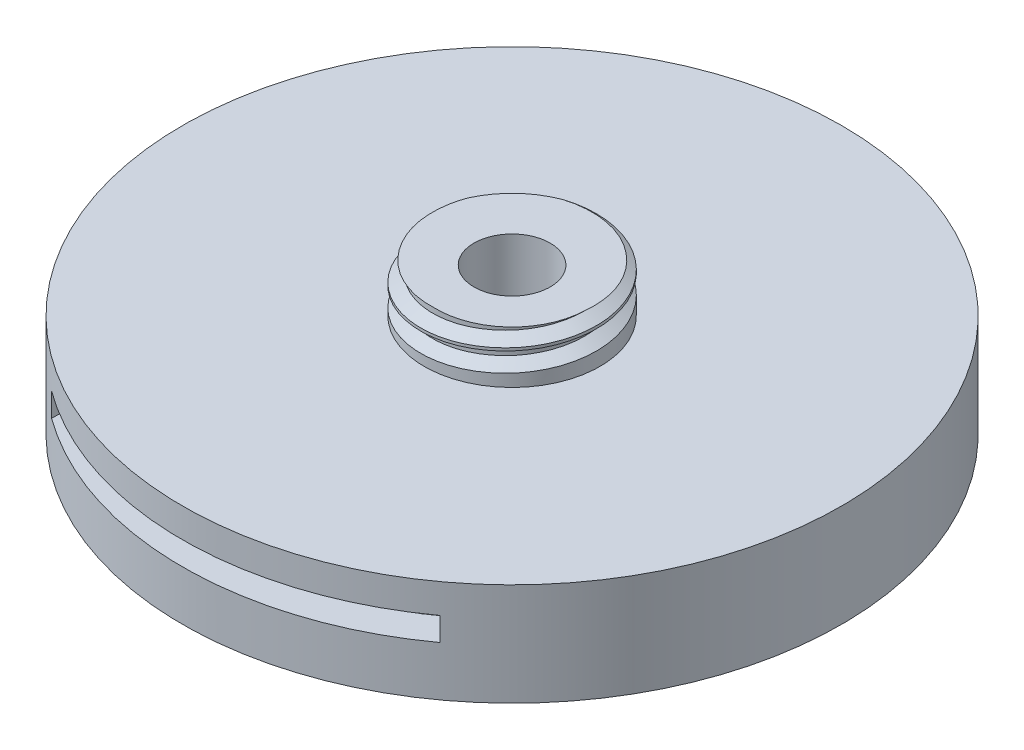
SolidWorks part; units mm, degrees
ref_plane "Ebene vorne" through (0, 0, 0) normal (0, 0, 1) x (1, 0, 0)
ref_plane "Ebene oben" through (0, 0, 0) normal (0, 1, 0) x (1, 0, 0)
ref_plane "Ebene rechts" through (0, 0, 0) normal (1, 0, 0) x (0, 0, -1)
sketch "Skizze1" plane through (0, 0, 0) normal (0, 1, 0) x (1, 0, 0)
  circle A0 centre (-18.0437, 0) radius 5
extrude "Zylinder" add sketch "Skizze1" along normal blind 2.2
ref_plane "Ebene auf Zylinder" through (0, 2.2, 0) normal (0, 1, 0) x (1, 0, 0)
sketch "Skizze4" plane through (0, 2.2, 0) normal (0, 1, 0) x (1, 0, 0)
  circle A0 centre (-18.0437, 0) radius 4.5
extrude "Schnitt-Linear austragen1" cut sketch "Skizze4" against normal blind 5 and the other way blind 10
ref_plane "Eben im Zylinder" through (0, 0.8, 0) normal (0, 1, 0) x (1, 0, 0)
sketch "Skizze5" plane through (0, 0.8, 0) normal (0, 1, 0) x (1, 0, 0)
  circle A0 centre (-18.0437, 0) radius 4.55
ref_plane "Ebene für Aufsatz" through (0, 0, 0) normal (0, -1, 0) x (-1, 0, 0)
sketch "Skizze6" plane through (0, 0, 0) normal (0, -1, 0) x (-1, 0, 0)
  circle A0 centre (18.0437, 0) radius 22.5
extrude "Fassung Objektträgergewinde" add sketch "Skizze6" along normal blind 7
ref_plane "Ebene auf Objektträgerfassung" through (0, -7, 0) normal (0, -1, 0) x (-1, 0, 0)
sketch "Skizze11" plane through (0, -7, 0) normal (0, -1, 0) x (-1, 0, 0)
  circle A0 centre (18.0437, 0) radius 20.3
extrude "Bohrung für Innengewinde" cut sketch "Skizze11" against normal blind 6
sketch "Skizze12" plane through (0, 0, 0) normal (0, -1, 0) x (-1, 0, 0)
  circle A2 centre (18.0437, 0) radius 4.5
ref_plane "Ebene1" through (0, 0, 0) normal (0, -1, 0) x (-1, 0, 0)
sketch "Skizze13" plane through (0, 0, 0) normal (0, -1, 0) x (-1, 0, 0)
  circle A0 centre (18.0437, 0) radius 6
  dimension "D1" = 12
extrude "Aufsatz-Linear austragen1" add sketch "Skizze13" against normal blind 3
ref_plane "Ebene4" through (0, -1, 0) normal (0, -1, 0) x (-1, 0, 0)
sketch "Skizze15" plane through (0, -1, 0) normal (0, -1, 0) x (-1, 0, 0)
  circle A0 centre (18.0437, 0) radius 9.2938
sketch "Skizze16" plane through (0, -7, 0) normal (0, -1, 0) x (-1, 0, 0)
  circle A0 centre (18.0437, 0) radius 2.6
extrude "Schnitt-Linear austragen13" cut sketch "Skizze16" against normal blind 10
thread "Gewinde1" pitch 1.5 method cut profile "Gewindeprofil1" start angle 0, offset 1.6, length 3.5, pitch 1.5, diameter 12
ref_plane "Ebene6" through (-24.0437, 4.6, 0) normal (0, 0, 1) x (-1, 0, 0)
sketch "Gewindeprofil1" plane through (-24.0437, 4.6, 0) normal (0, 0, 1) x (-1, 0, 0)
  line L0 (0, 0) -> (0, 1.5) construction
  line L11 (0, 0) -> (0, 1.3125)
  line L12 (0, 1.3125) -> (-0.8119, 0.8437)
  line L13 (-0.8119, 0.8437) -> (-0.8119, 0.4687)
  line L15 (-0.8119, 0.4687) -> (0, 0)
  line L17 (-0.8119, 0.6562) -> (0, 0.6562) construction
  point P2 (0, 0)
  dimension "Pitch" = 1.5
  dimension "Profile_Angle" = 60
  dimension "Profile_Land" = 0.375
  dimension "Profile_Height" = 0.8119
ref_plane "Ebene7" through (0, -2, 0) normal (0, 1, 0) x (1, 0, 0)
sketch "Skizze17" plane through (0, -2, 0) normal (0, 1, 0) x (1, 0, 0)
  line L1 (-4.7937, -24.7706) -> (-31.2937, -24.7706)
  line L2 (-4.7937, -24.7706) -> (-4.7937, 24.7706)
  line L3 (-4.7937, 24.7706) -> (-31.2937, 24.7706)
  line L4 (-31.2937, -24.7706) -> (-31.2937, 24.7706)
  line L5 (-4.7937, -24.7706) -> (-31.2937, 24.7706) construction
  line L6 (-4.7937, 24.7706) -> (-31.2937, -24.7706) construction
  point P0 (-18.0437, 0)
  dimension "D1" = 26.5
extrude "Schnitt-Linear austragen14" cut sketch "Skizze17" against normal blind 1.6
ref_plane "Ebene für Schrift" through (0, 0, 0) normal (0, 1, 0) x (1, 0, 0)
